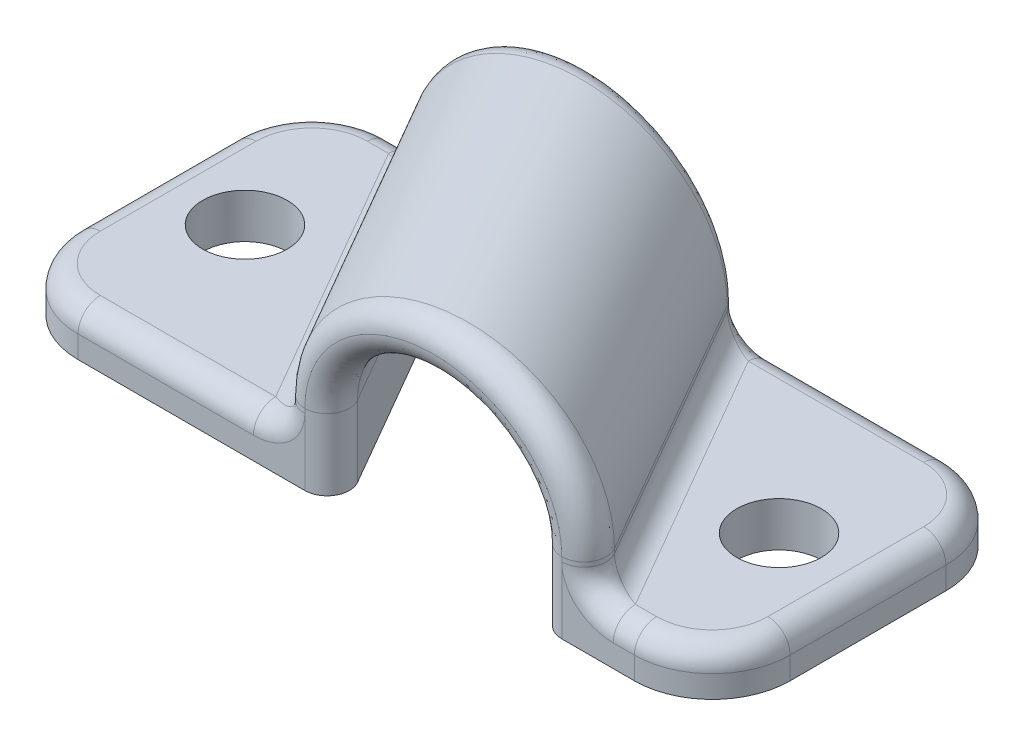
SolidWorks part; units mm, degrees
material "PLA"
ref_plane "Alzado" through (0, 0, 0) normal (0, 0, 1) x (1, 0, 0)
ref_plane "Planta" through (0, 0, 0) normal (0, 1, 0) x (1, 0, 0)
ref_plane "Vista lateral" through (0, 0, 0) normal (1, 0, 0) x (0, 0, -1)
sketch "Croquis1" plane through (0, 0, 0) normal (0, 0, 1) x (1, 0, 0)
  line L0 (-3.6, 0) -> (-3.6, -3.6)
  line L1 (-3.6, -3.6) -> (-16, -3.6)
  line L2 (3.6, 0) -> (3.6, -3.6)
  line L3 (3.6, -3.6) -> (16, -3.6)
  line L4 (0, 0) -> (0, 3.7743) construction
  line L5 (-12, -3.6) -> (-12, -1.1244) construction
  line L6 (5.6, -1.6) -> (16, -1.6)
  line L7 (5.6, 0) -> (5.6, -1.6)
  line L8 (-5.6, 0) -> (-5.6, -1.6)
  line L9 (-5.6, -1.6) -> (-16, -1.6)
  line L10 (-16, -3.6) -> (-16, -1.6)
  line L11 (16, -3.6) -> (16, -1.6)
  arc A0 (3.6, 0) -> (-3.6, 0) centre (0, 0) ccw
  arc A1 (5.6, 0) -> (-5.6, 0) centre (0, 0) ccw
  dimension "D1" = 7.2
  dimension "D2" = 2
  dimension "D3" = 24
  dimension "D4" = 32
sketch "Croquis2" plane through (0, 0, 0) normal (0, 0, 1) x (1, 0, 0)
  line L1 (-16, -3.6) -> (16, -3.6)
  line L2 (-16, -3.6) -> (-16, 5.6)
  line L3 (-16, 5.6) -> (16, 5.6)
  line L4 (16, -3.6) -> (16, 5.6)
  arc A0 (5.6, 0) -> (-5.6, 0) centre (0, 0) ccw construction
extrude "Saliente-Extruir1" add sketch "Croquis2" along normal blind 14
sketch "Croquis3" plane through (0, -3.6, 0) normal (0, -1, 0) x (1, 0, 0)
  line L0 (-16, 7) -> (16, 7) construction
  line L1 (-16, 14) -> (-16, 0) construction
  line L2 (16, 14) -> (16, 0) construction
  line L3 (-4.0415, 0) -> (4.0415, 14) construction
  line L4 (-16, 0) -> (16, 0) construction
  line L5 (-16, 14) -> (16, 14) construction
  line L6 (-8.6603, 0) -> (1.7321, 18)
  line L7 (1.7321, 18) -> (8.6603, 14)
  line L8 (8.6603, 14) -> (-1.7321, -4)
  line L9 (-1.7321, -4) -> (-8.6603, 0)
  line L10 (4.0415, 14) -> (5.1962, 16) construction
  line L11 (-5.6, 0) -> (-16, 0) construction
  point P12 (0, 7)
  dimension "D1" = 60
  dimension "D2" = 8
extrude "Cortar-Extruir1" cut sketch "Croquis3" against normal blind 7.2
sketch "Croquis4" plane through (0, -3.6, 0) normal (0, -1, 0) x (1, 0, 0)
  line L0 (-12, 0) -> (-12, 14) construction
  line L2 (-16, 14) -> (-0.5774, 14) construction
  line L3 (0, 0) -> (0, 14.8809) construction
  circle A0 centre (-12, 7) radius 1.9
  circle A1 centre (12, 7) radius 1.9
  dimension "D1" = 3.8
extrude "Cortar-Extruir2" cut sketch "Croquis4" against normal through all
fillet "Redondeo1" 2 edges at (-4.6188, 3.6, 7) (4.6188, 3.6, 7) type full round first side face at (-4.6188, 0, 7) second side face at (4.6188, 0, 7) middle face at (0, 3.6, 7)
ref_plane "Plano1" through (-8.6603, -3.6, 0) normal (-0.5, 0, -0.866) x (-0.866, 0, 0.5)
sketch "Croquis5" plane through (-8.6603, -3.6, 0) normal (-0.5, 0, -0.866) x (-0.866, 0, 0.5)
  line L2 (-10, 2) -> (-21.3564, 2)
  line L3 (-21.3564, 2) -> (-21.3564, 0)
  line L4 (2, 0) -> (2, 3.2)
  line L5 (-10, 3.2) -> (-10, 0)
  line L6 (2, 2) -> (2, 3.2)
  line L7 (-10, 3.2) -> (-10, 2)
  line L8 (-21.3564, 0) -> (13.3564, 0)
  line L9 (13.3564, 0) -> (13.3564, 2)
  line L10 (13.3564, 2) -> (2, 2)
  line L11 (6.3564, 0) -> (0, 0) construction
  line L12 (-21.3564, 0) -> (-21.3564, 9.2) construction
  line L13 (13.3564, 9.2) -> (13.3564, 0) construction
  arc A2 (2, 3.2) -> (-10, 3.2) centre (-4, 3.2) ccw
  arc A3 (2, 3.2) -> (-10, 3.2) centre (-4, 3.2) ccw
  dimension "D2" = 2
  dimension "D1" = 2
extrude "Cortar-Extruir3" cut sketch "Croquis5" against normal through all and the other way through all flip side to cut
fillet "Redondeo2" radius 3.5 4 edges at (-16, -2.6, 0) (-16, -2.6, 14) (16, -2.6, 0) (16, -2.6, 14)
fillet "Redondeo3" radius 1 24 edges at (4.0415, 5.6, 14) (-2.8868, -1, 14) (10.9697, -1, 14) (-7.6934, -1.6, 14) (11.7348, -1.6, 14) (-14.9749, -1.6, 12.9749) (14.9749, -1.6, 12.9749) (-16, -1.6, 7) (16, -1.6, 7) (-14.9749, -1.6, 1.0251) (14.9749, -1.6, 1.0251) (-11.7348, -1.6, 0) (7.6934, -1.6, 0) (-10.9697, -1, 0) (2.8868, -1, 0) (8.6603, -2, 14) (-0.5774, -2, 14) (-8.6603, -2, 0) (0.5774, -2, 0) (-4.0415, 5.6, 0) (-6.9282, -1.6, 7) (6.9282, -1.6, 7) (4.0415, 3.6, 14) (-4.0415, 3.6, 0)
ref_axis "Eje de abrazadera" through (4.9075, -0.4, 15.5) along (-0.5, 0, -0.866)
ref_plane "Plano2" through (0, -0.1, 0) normal (0, 1, 0) x (1, 0, 0)
sketch "Croquis8" plane through (0, -0.1, 0) normal (0, 1, 0) x (1, 0, 0)
  line L0 (4.9075, -15.5) -> (-4.9075, 1.5) construction
  point P0 (-3.7528, -0.5)
  point P1 (2.0098, -10.4811)
other "PuntoR1"
other "PuntoR2"
